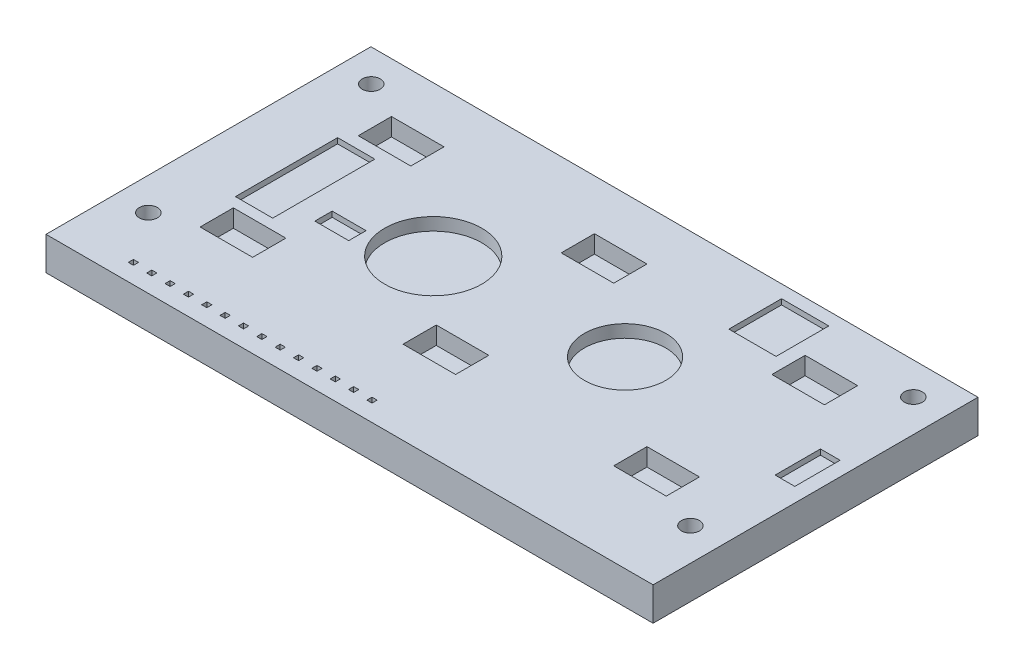
SolidWorks part; units mm, degrees
ref_plane "Front Plane" through (0, 0, 0) normal (0, 0, 1) x (1, 0, 0)
ref_plane "Top Plane" through (0, 0, 0) normal (0, 1, 0) x (1, 0, 0)
ref_plane "Right Plane" through (0, 0, 0) normal (1, 0, 0) x (0, 0, -1)
sketch "Sketch1" plane through (0, 0, 0) normal (0, 1, 0) x (1, 0, 0)
  line L1 (0, 0) -> (-84.03, 0)
  line L2 (0, 0) -> (0, -44.97)
  line L3 (0, -44.97) -> (-84.03, -44.97)
  line L4 (-84.03, 0) -> (-84.03, -44.97)
  line L5 (-74.97, -41.93) -> (-74.26, -41.93)
  line L6 (-74.97, -41.93) -> (-74.97, -42.64)
  line L7 (-74.97, -42.64) -> (-74.26, -42.64)
  line L8 (-74.26, -41.93) -> (-74.26, -42.64)
  line L9 (-72.43, -41.93) -> (-71.72, -41.93)
  line L10 (-72.43, -41.93) -> (-72.43, -42.64)
  line L11 (-72.43, -42.64) -> (-71.72, -42.64)
  line L12 (-71.72, -41.93) -> (-71.72, -42.64)
  line L13 (-69.89, -41.93) -> (-69.18, -41.93)
  line L14 (-69.89, -41.93) -> (-69.89, -42.64)
  line L15 (-69.89, -42.64) -> (-69.18, -42.64)
  line L16 (-69.18, -41.93) -> (-69.18, -42.64)
  line L17 (-67.35, -41.93) -> (-66.64, -41.93)
  line L18 (-67.35, -41.93) -> (-67.35, -42.64)
  line L19 (-67.35, -42.64) -> (-66.64, -42.64)
  line L20 (-66.64, -41.93) -> (-66.64, -42.64)
  line L21 (-64.81, -41.93) -> (-64.1, -41.93)
  line L22 (-64.81, -41.93) -> (-64.81, -42.64)
  line L23 (-64.81, -42.64) -> (-64.1, -42.64)
  line L24 (-64.1, -41.93) -> (-64.1, -42.64)
  line L25 (-62.27, -41.93) -> (-61.56, -41.93)
  line L26 (-62.27, -41.93) -> (-62.27, -42.64)
  line L27 (-62.27, -42.64) -> (-61.56, -42.64)
  line L28 (-61.56, -41.93) -> (-61.56, -42.64)
  line L29 (-59.73, -41.93) -> (-59.02, -41.93)
  line L30 (-59.73, -41.93) -> (-59.73, -42.64)
  line L31 (-59.73, -42.64) -> (-59.02, -42.64)
  line L32 (-59.02, -41.93) -> (-59.02, -42.64)
  line L33 (-57.19, -41.93) -> (-56.48, -41.93)
  line L34 (-57.19, -41.93) -> (-57.19, -42.64)
  line L35 (-57.19, -42.64) -> (-56.48, -42.64)
  line L36 (-56.48, -41.93) -> (-56.48, -42.64)
  line L37 (-54.65, -41.93) -> (-53.94, -41.93)
  line L38 (-54.65, -41.93) -> (-54.65, -42.64)
  line L39 (-54.65, -42.64) -> (-53.94, -42.64)
  line L40 (-53.94, -41.93) -> (-53.94, -42.64)
  line L41 (-52.11, -41.93) -> (-51.4, -41.93)
  line L42 (-52.11, -41.93) -> (-52.11, -42.64)
  line L43 (-52.11, -42.64) -> (-51.4, -42.64)
  line L44 (-51.4, -41.93) -> (-51.4, -42.64)
  line L45 (-49.57, -41.93) -> (-48.86, -41.93)
  line L46 (-49.57, -41.93) -> (-49.57, -42.64)
  line L47 (-49.57, -42.64) -> (-48.86, -42.64)
  line L48 (-48.86, -41.93) -> (-48.86, -42.64)
  line L49 (-47.03, -41.93) -> (-46.32, -41.93)
  line L50 (-47.03, -41.93) -> (-47.03, -42.64)
  line L51 (-47.03, -42.64) -> (-46.32, -42.64)
  line L52 (-46.32, -41.93) -> (-46.32, -42.64)
  line L53 (-44.49, -41.93) -> (-43.78, -41.93)
  line L54 (-44.49, -41.93) -> (-44.49, -42.64)
  line L55 (-44.49, -42.64) -> (-43.78, -42.64)
  line L56 (-43.78, -41.93) -> (-43.78, -42.64)
  line L57 (-41.95, -41.93) -> (-41.24, -41.93)
  line L58 (-41.95, -41.93) -> (-41.95, -42.64)
  line L59 (-41.95, -42.64) -> (-41.24, -42.64)
  line L60 (-41.24, -41.93) -> (-41.24, -42.64)
  dimension "D1" = 0.71
  dimension "D2" = 2.54
  dimension "D3" = 2.54
  dimension "D4" = 2.54
  dimension "D5" = 2.54
  dimension "D6" = 2.54
  dimension "D7" = 2.54
  dimension "D8" = 2.54
  dimension "D9" = 2.54
  dimension "D10" = 2.54
  dimension "D11" = 2.54
  dimension "D12" = 2.54
  dimension "D13" = 2.54
  dimension "D14" = 2.54
  dimension "D15" = 44.97
  dimension "D16" = 84.03
  dimension "D17" = 9.06
  dimension "D18" = 2.33
extrude "Boss-Extrude1" add sketch "Sketch1" along normal blind 4.61
sketch "Sketch2" plane through (0, 4.61, 0) normal (0, 1, 0) x (1, 0, 0)
  line L0 (-84.03, 0) -> (-84.03, -44.97) construction
  line L1 (-82.03, -1.78) -> (-1.99, -1.78)
  line L2 (-82.03, -1.78) -> (-82.03, -37.83)
  line L3 (-82.03, -37.83) -> (-1.99, -37.83)
  line L4 (-1.99, -1.78) -> (-1.99, -37.83)
  line L5 (0, 0) -> (-84.03, 0) construction
  line L7 (-16.99, -6.94) -> (-9.72, -6.94)
  line L8 (-16.99, -6.94) -> (-16.99, -11.54)
  line L9 (-16.99, -11.54) -> (-9.72, -11.54)
  line L10 (-9.72, -6.94) -> (-9.72, -11.54)
  line L11 (-46.15, -6.94) -> (-38.88, -6.94)
  line L12 (-46.15, -6.94) -> (-46.15, -11.54)
  line L13 (-46.15, -11.54) -> (-38.88, -11.54)
  line L14 (-38.88, -6.94) -> (-38.88, -11.54)
  line L15 (-74.24, -6.94) -> (-66.97, -6.94)
  line L16 (-74.24, -6.94) -> (-74.24, -11.54)
  line L17 (-74.24, -11.54) -> (-66.97, -11.54)
  line L18 (-66.97, -6.94) -> (-66.97, -11.54)
  line L19 (-74.24, -28.83) -> (-66.97, -28.83)
  line L20 (-74.24, -28.83) -> (-74.24, -33.43)
  line L21 (-74.24, -33.43) -> (-66.97, -33.43)
  line L22 (-66.97, -28.83) -> (-66.97, -33.43)
  line L23 (-46.15, -28.83) -> (-38.88, -28.83)
  line L24 (-46.15, -28.83) -> (-46.15, -33.43)
  line L25 (-46.15, -33.43) -> (-38.88, -33.43)
  line L26 (-38.88, -28.83) -> (-38.88, -33.43)
  line L27 (-16.99, -28.83) -> (-9.72, -28.83)
  line L28 (-16.99, -28.83) -> (-16.99, -33.43)
  line L29 (-16.99, -33.43) -> (-9.72, -33.43)
  line L30 (-9.72, -28.83) -> (-9.72, -33.43)
  line L31 (-1.99, -23.37) -> (-4.71, -23.37)
  line L32 (-1.99, -23.37) -> (-1.99, -17.1)
  line L33 (-1.99, -17.1) -> (-4.71, -17.1)
  line L34 (-4.71, -23.37) -> (-4.71, -17.1)
  line L35 (-25.41, -1.78) -> (-18.87, -1.78)
  line L36 (-25.41, -1.78) -> (-25.41, -9.08)
  line L37 (-25.41, -9.08) -> (-18.87, -9.08)
  line L38 (-18.87, -1.78) -> (-18.87, -9.08)
  line L39 (-75.44, -13.2) -> (-70.28, -13.2)
  line L40 (-75.44, -13.2) -> (-75.44, -27.34)
  line L41 (-75.44, -27.34) -> (-70.28, -27.34)
  line L42 (-70.28, -13.2) -> (-70.28, -27.34)
  line L43 (-67.01, -22.38) -> (-62.32, -22.38)
  line L44 (-67.01, -22.38) -> (-67.01, -24.78)
  line L45 (-67.01, -24.78) -> (-62.32, -24.78)
  line L46 (-62.32, -22.38) -> (-62.32, -24.78)
  circle A0 centre (-79.535, -4.45) radius 1.25
  circle A1 centre (-79.535, -35.3) radius 1.25
  circle A2 centre (-4.5, -4.45) radius 1.25
  circle A3 centre (-4.5, -35.3) radius 1.25
  circle A4 centre (-54.61, -20.79) radius 6.72
  circle A5 centre (-29.26, -19.59) radius 5.64
  point P60 (0, 0)
  point P61 (0, 0)
  point P62 (-70.28, -20.9845)
  dimension "D5" = 2.5
  dimension "D6" = 2.5
  dimension "D7" = 2.5
  dimension "D8" = 2.5
  dimension "D36" = 13.44
  dimension "D39" = 11.28
  dimension "D1" = 36.05
  dimension "D2" = 80.04
  dimension "D3" = 2
  dimension "D4" = 1.78
  dimension "D9" = 2.51
  dimension "D10" = 2.495
  dimension "D11" = 2.67
  dimension "D12" = 2.53
  dimension "D13" = 7.27
  dimension "D14" = 4.6
  dimension "D15" = 5.16
  dimension "D16" = 4.4
  dimension "D17" = 7.79
  dimension "D18" = 7.73
  dimension "D19" = 36.89
  dimension "D20" = 16.88
  dimension "D21" = 23.42
  dimension "D22" = 7.3
  dimension "D23" = 15.32
  dimension "D24" = 21.59
  dimension "D25" = 2.72
  dimension "D26" = 6.59
  dimension "D27" = 11.75
  dimension "D28" = 25.56
  dimension "D29" = 11.42
  dimension "D30" = 15.02
  dimension "D31" = 19.71
  dimension "D32" = 20.6
  dimension "D33" = 23
  dimension "D34" = 19.01
  dimension "D35" = 27.42
  dimension "D37" = 17.81
  dimension "D38" = 27.27
extrude "Cut-Extrude1" cut sketch "Sketch2" against normal up to next contours A0 | A2 | A3 | A1 region at (-79.535, 4.61, 4.45) region at (-79.535, 4.61, 35.3) region at (-4.5, 4.61, 4.45) region at (-4.5, 4.61, 35.3)
extrude "Cut-Extrude2" cut sketch "Sketch2<3>" against normal blind 2.45 contours L18 L15 L16 L17 | L14 L11 L12 L13 | L10 L7 L8 L9 | L30 L27 L28 L29 | L26 L23 L24 L25 | L22 L19 L20 L21 region at (-13.355, 4.61, 9.24) region at (-42.515, 4.61, 9.24) region at (-70.605, 4.61, 9.24) region at (-70.605, 4.61, 31.13) region at (-42.515, 4.61, 31.13) region at (-13.355, 4.61, 31.13)
sketch "Sketch2<3>" plane through (0, 4.61, 0) normal (0, 1, 0) x (1, 0, 0) same geometry as "Sketch2"
extrude "Cut-Extrude3" cut sketch "Sketch2<4>" against normal blind 1.75 contours A4 | A5 region at (-54.61, 4.61, 20.79) region at (-29.26, 4.61, 19.59)
sketch "Sketch2<4>" plane through (0, 4.61, 0) normal (0, 1, 0) x (1, 0, 0) same geometry as "Sketch2"
extrude "Cut-Extrude4" cut sketch "Sketch2<5>" against normal blind 0.75 contours L42 L39 L40 L41 | L46 L43 L44 L45 | L38 L1 L36 L37 | L34 L31 L4 L33 region at (-22.14, 4.61, 5.43) region at (-3.35, 4.61, 20.235) region at (-72.86, 4.61, 20.27) region at (-64.665, 4.61, 23.58)
sketch "Sketch2<5>" plane through (0, 4.61, 0) normal (0, 1, 0) x (1, 0, 0) same geometry as "Sketch2"
